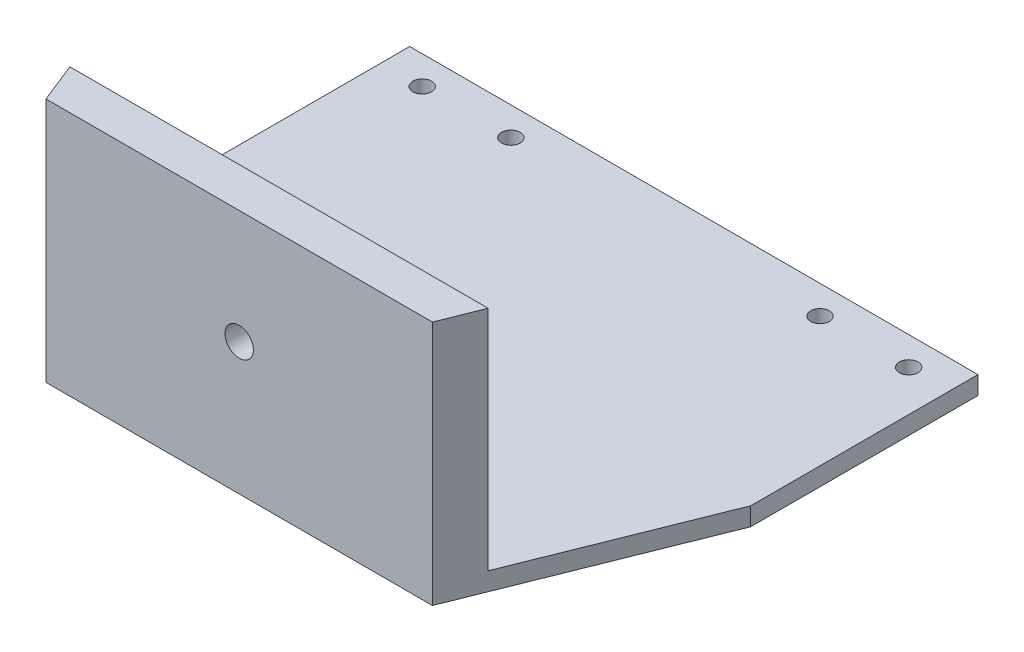
SolidWorks part; units mm, degrees
ref_plane "Front Plane" through (0, 0, 0) normal (0, 0, 1) x (1, 0, 0)
ref_plane "Top Plane" through (0, 0, 0) normal (0, 1, 0) x (1, 0, 0)
ref_plane "Right Plane" through (0, 0, 0) normal (1, 0, 0) x (0, 0, -1)
sketch "Sketch1" plane through (0, 0, 0) normal (0, 1, 0) x (1, 0, 0)
  line L0 (-63.5, -25.4) -> (-43.18, -76.2)
  line L1 (-63.5, -25.4) -> (63.5, -25.4)
  line L2 (-63.5, -25.4) -> (-63.5, 25.4)
  line L3 (-63.5, 25.4) -> (63.5, 25.4)
  line L4 (63.5, -25.4) -> (63.5, 25.4)
  line L5 (-63.5, -25.4) -> (63.5, 25.4) construction
  line L6 (-63.5, 25.4) -> (63.5, -25.4) construction
  line L7 (-43.18, -76.2) -> (43.18, -76.2)
  line L8 (43.18, -76.2) -> (63.5, -25.4)
  circle A0 centre (-54.356, 19.05) radius 2.0828
  circle A1 centre (-34.544, 19.05) radius 2.0828
  circle A2 centre (34.544, 19.05) radius 2.0828
  circle A3 centre (54.356, 19.05) radius 2.0828
  point P0 (0, 0)
  dimension "D4" = 4.1656
  dimension "D5" = 4.1656
  dimension "D6" = 4.1656
  dimension "D7" = 4.1656
  dimension "D8" = 6.35
  dimension "D9" = 9.144
  dimension "D10" = 19.812
  dimension "D11" = 9.144
  dimension "D12" = 19.812
  dimension "D1" = 127
  dimension "D2" = 50.8
  dimension "D3" = 50.8
extrude "Boss-Extrude1" add sketch "Sketch1" along normal mid plane 4.064 contours L1 L4 L3 L2 A3 A2 A1 A0 | L7 L8 L1 L0 region at (0, 0, 49.1873) region at (0, 0, 0.1623)
sketch "Sketch2" plane through (0, 2.032, 0) normal (0, 1, 0) x (1, 0, 0)
  line L0 (-43.18, -76.2) -> (-46.736, -67.31)
  line L1 (-63.5, -25.4) -> (-43.18, -76.2) construction
  line L2 (-46.736, -67.31) -> (46.736, -67.31)
  line L3 (46.736, -67.31) -> (43.18, -76.2)
  line L4 (43.18, -76.2) -> (63.5, -25.4) construction
  line L6 (-43.18, -76.2) -> (43.18, -76.2)
  line L7 (43.18, -76.2) -> (43.2009, -76.2047)
  line M8 (-63.5, -25.4) -> (-43.18, -76.2)
  line M9 (-43.18, -76.2) -> (43.18, -76.2)
  line M10 (43.18, -76.2) -> (63.5, -25.4)
  dimension "D1" = 8.89
extrude "Boss-Extrude2" add sketch "Sketch2" along normal blind 50.8 contours L2 M8 M9 M10 region at (0, 2.032, 71.6964)
sketch "Sketch3" plane through (0, 0, 67.31) normal (0, 0, -1) x (-1, 0, 0)
  line L1 (46.736, 2.032) -> (-46.736, 52.832)
  line L2 (-46.736, 2.032) -> (46.736, 52.832)
  circle A0 centre (0, 27.432) radius 3.175
  dimension "D1" = 6.35
  dimension "D2" = 0
  dimension "D3" = 0
extrude "Cut-Extrude1" cut sketch "Sketch3" against normal through all contours L2 A0 L1 | L1 A0 L2 | L2 A0 L1 | L1 A0 L2 region at (0, 25.6987, 67.31) region at (-2.0303, 27.432, 67.31) region at (2.0303, 27.432, 67.31) region at (0, 29.1653, 67.31)
